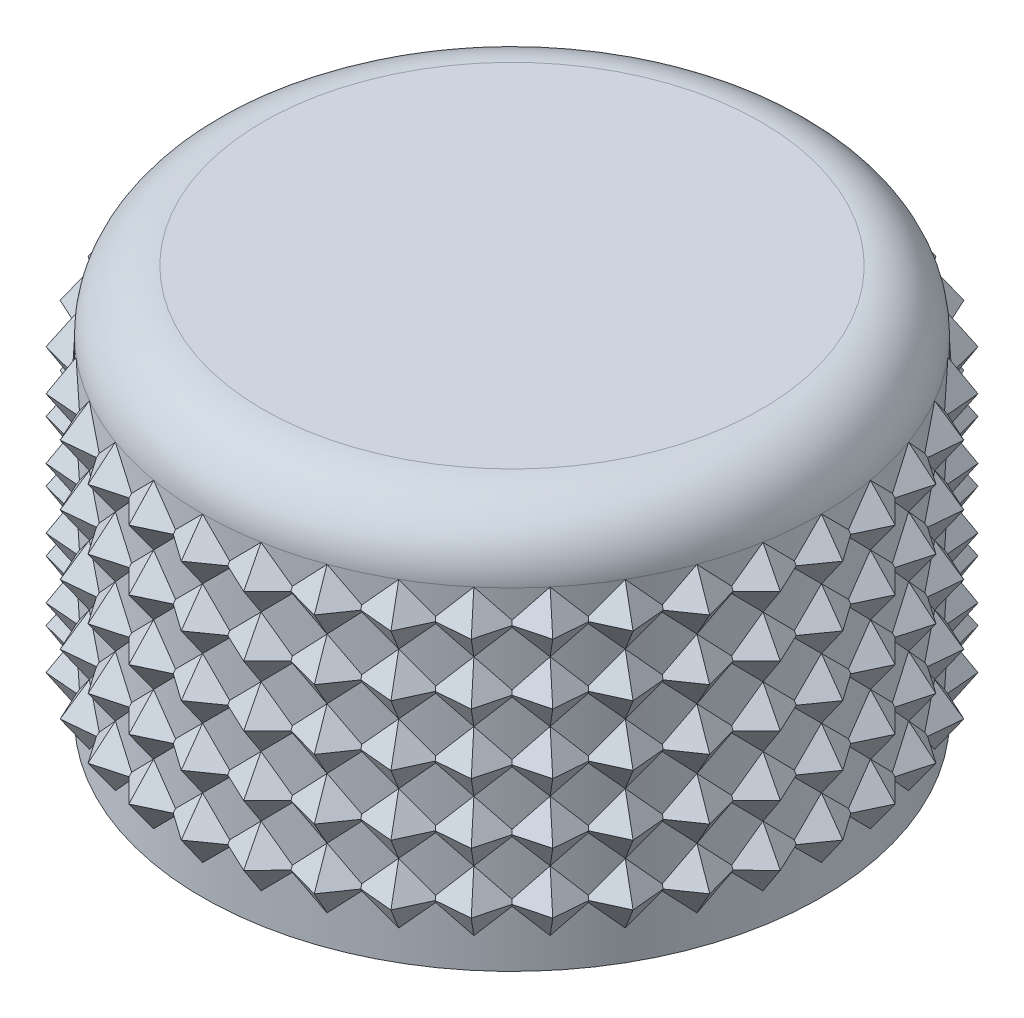
SolidWorks part; units mm, degrees
ref_plane "Front Plane" through (0, 0, 0) normal (0, 0, 1) x (1, 0, 0)
ref_plane "Top Plane" through (0, 0, 0) normal (0, 1, 0) x (1, 0, 0)
ref_plane "Right Plane" through (0, 0, 0) normal (1, 0, 0) x (0, 0, -1)
sketch "Sketch4" plane through (0, 0, 0) normal (0, 1, 0) x (1, 0, 0)
  circle A0 centre (0, 0) radius 10.25
extrude "Boss-Extrude4" add sketch "Sketch4" along normal blind 13
sketch "Sketch5" plane through (0, 0, 0) normal (0, 1, 0) x (1, 0, 0)
  circle A0 centre (0, 0) radius 8
  circle A1 centre (0, 0) radius 4
extrude "Cut-Extrude2" cut sketch "Sketch5" along normal blind 12
sketch "Sketch6" plane through (0, 0, 0) normal (0, -1, 0) x (1, 0, 0)
  circle A0 centre (0, 0) radius 3.1
extrude "Cut-Extrude3" cut sketch "Sketch6" against normal blind 5
sketch "Sketch7" plane through (0, 0, 0) normal (0, -1, 0) x (1, 0, 0)
  circle A0 centre (0, 0) radius 4
extrude "Cut-Extrude4" cut sketch "Sketch7" against normal blind 2
sketch "Sketch9" plane through (0, 0, 0) normal (0, -1, 0) x (1, 0, 0)
  line L0 (0, -3.1) -> (0, 1.45) construction
  line L1 (0, 1.45) -> (2.74, 1.45)
  line L2 (2.74, 1.45) -> (0, 1.45)
  line L3 (0, 1.45) -> (-2.74, 1.45)
  circle A0 centre (0, 0) radius 3.1 construction
  circle A1 centre (0, 0) radius 3.1 construction
  circle A2 centre (0, 0) radius 3.1
extrude "Cut-Extrude5" cut sketch "Sketch9" against normal blind 12 contours A2 L0 L3 | L0 A2 L1 region at (-1.3804, 0, -0.5775) region at (1.3804, 0, -0.5775)
sketch "Sketch10" plane through (0, 0, 0) normal (0, -1, 0) x (1, 0, 0)
  line L0 (0, 0) -> (0, 10.25)
  circle A0 centre (0, 0) radius 10.25 construction
ref_plane "Plane1" through (0, 0, 10.25) normal (0, 0, 1) x (1, 0, 0)
fillet "Fillet2" radius 2 1 edges at (0, 13, 10.25)
sketch "Sketch11" plane through (0, 0, 10.25) normal (0, 0, 1) x (1, 0, 0)
  line L0 (1, 10) -> (0, 11)
  line L1 (1, 10) -> (0, 9)
  line L2 (0, 11) -> (-1, 10)
  line L3 (0, 9) -> (-1, 10)
  line L4 (1, 10) -> (-1, 10) construction
  line L5 (0, 11) -> (0, 9) construction
  line L6 (0, 0) -> (0, 11)
  line L7 (1, 8) -> (0, 9)
  line L8 (1, 8) -> (0, 7)
  line L9 (0, 7) -> (-1, 8)
  line L10 (0, 9) -> (-1, 8)
  line L11 (1, 6) -> (0, 7)
  line L12 (1, 6) -> (0, 5)
  line L13 (0, 5) -> (-1, 6)
  line L14 (0, 7) -> (-1, 6)
  line L15 (1, 4) -> (0, 5)
  line L16 (1, 4) -> (0, 3)
  line L17 (0, 3) -> (-1, 4)
  line L18 (0, 5) -> (-1, 4)
  line L19 (1, 2) -> (0, 3)
  line L20 (1, 2) -> (0, 1)
  line L21 (0, 1) -> (-1, 2)
  line L22 (0, 3) -> (-1, 2)
  point P1 (0, 10)
  dimension "D1" = 5
extrude "Boss-Extrude5" add sketch "Sketch11" along normal blind 1 draft 45 separate body contours L6 L1 L0 | L3 L6 L2 | L8 L7 L6 | L6 L10 L9 | L6 L14 L13 | L12 L11 L6 | L16 L15 L6 | L6 L18 L17 | L6 L22 L21 | L20 L19 L6 region at (0.3333, 10, 10.25) region at (0.3333, 2, 10.25) region at (-0.3333, 2, 10.25) region at (0.3333, 4, 10.25) region at (-0.3333, 4, 10.25) region at (0.3333, 6, 10.25) region at (-0.3333, 6, 10.25) region at (0.3333, 8, 10.25) region at (-0.3333, 8, 10.25) region at (-0.3333, 10, 10.25)
pattern_circular "CirPattern1" count 36 over 360 about axis through (0, 13, 0) along (0, 1, 0) of "Boss-Extrude5"
